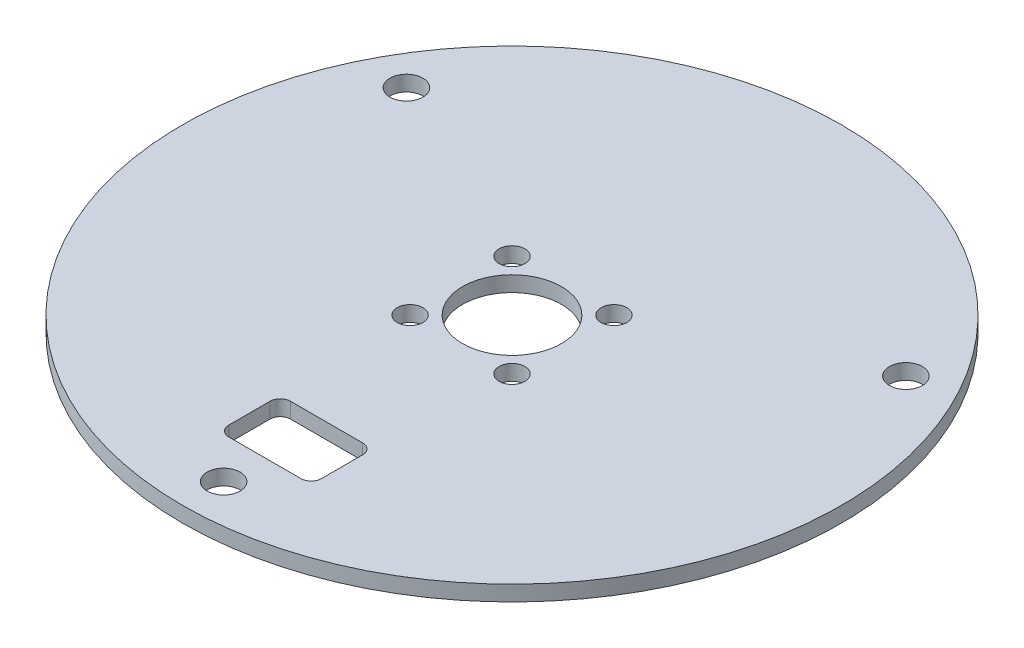
SolidWorks part; units mm, degrees
note: The reader was unsure of these and kept them because the rebuilt part matched: thickness of "Base-Flange1", "Sheet-Metal1", "Sheet-Metal2", "Sheet-Metal3", "Sheet-Metal4".
ref_plane "Front Plane" through (0, 0, 0) normal (0, 0, 1) x (1, 0, 0)
ref_plane "Top Plane" through (0, 0, 0) normal (0, 1, 0) x (1, 0, 0)
ref_plane "Right Plane" through (0, 0, 0) normal (1, 0, 0) x (0, 0, -1)
sketch "Sketch1" plane through (0, 0, 0) normal (0, 1, 0) x (1, 0, 0)
  circle A1 centre (0, 0) radius 32
  dimension "D2" = 64
base flange "Base-Flange1" sketch "Sketch1" thickness 1.5 reverse thickness direction no parameters "D1"=1.5
sketch "Sketch6" plane through (0, 0, 0) normal (0, 1, 0) x (1, 0, 0)
  line L0 (0, 0) -> (0, -28) construction
  line L5 (0, 0) -> (-24.2487, 14) construction
  line L7 (0, 0) -> (24.2487, 14) construction
  circle A10 centre (0, -28) radius 1.6
  circle A11 centre (-24.2487, 14) radius 1.6
  circle A12 centre (24.2487, 14) radius 1.6
  point P9 (0, 0)
  dimension "D1" = 28
  dimension "D2" = 3
  dimension "D3" = 3.2
extrude "Cut-Extrude1" cut sketch "Sketch6" against normal through all normal cut yes
sketch "Sketch7" plane through (0, 0, 0) normal (0, 1, 0) x (1, 0, 0)
  line L1 (4.9497, -4.9497) -> (-4.9497, -4.9497) construction
  line L2 (4.9497, -4.9497) -> (4.9497, 4.9497) construction
  line L3 (4.9497, 4.9497) -> (-4.9497, 4.9497) construction
  line L4 (-4.9497, -4.9497) -> (-4.9497, 4.9497) construction
  line L5 (4.9497, -4.9497) -> (-4.9497, 4.9497) construction
  line L6 (4.9497, 4.9497) -> (-4.9497, -4.9497) construction
  circle A0 centre (0, 0) radius 4.8
  circle A1 centre (-4.9497, 4.9497) radius 1.25
  circle A2 centre (4.9497, 4.9497) radius 1.25
  circle A3 centre (4.9497, -4.9497) radius 1.25
  circle A4 centre (-4.9497, -4.9497) radius 1.25
  dimension "D1" = 9.6
  dimension "D2" = 2.5
  dimension "D3" = 14
extrude "Cut-Extrude2" cut sketch "Sketch7" against normal through all normal cut yes
sketch "Sketch9" plane through (0, 0, 0) normal (0, 1, 0) x (1, 0, 0)
  line L0 (-4.5, -21) -> (4.5, -21) construction
  line L1 (-4.5, -18) -> (4.5, -18)
  line L2 (-4.5, -18) -> (-4.5, -24)
  line L3 (-4.5, -24) -> (4.5, -24)
  line L4 (4.5, -18) -> (4.5, -24)
  point P4 (0, -18)
  dimension "D1" = 6
  dimension "D2" = 9
  dimension "D3" = 21
extrude "Cut-Extrude3" cut sketch "Sketch9" against normal through all normal cut yes
fillet "Fillet1" radius 1 4 edges at (-4.5, -0.75, 24) (4.5, -0.75, 24) (-4.5, -0.75, 18) (4.5, -0.75, 18)
sketch "Bend-Lines1" [suppressed] plane through (0, 0, 0) normal (0, 1, 0) x (1, 0, 0)
sketch "Bounding-Box1" [suppressed] plane through (0, 0, 0) normal (0, 1, 0) x (1, 0, 0)
sheet metal parameters "Sheet-Metal1" thickness 1.5 parameters "D1"=2, "D7"=2
flat pattern "Flat-Pattern1" [suppressed]
sketch "Bend-Lines2" plane through (0, 0, 0) normal (0, 1, 0) x (1, 0, 0)
sketch3d "Bounding-Box2" [suppressed]
  line L0 (32.05, -31.9499, 0) -> (-31.9499, -32.0499, 0) construction
  line L1 (31.95, 32.05, 0) -> (-32.0499, 31.95, 0) construction
  line L2 (32.05, -31.9499, 0) -> (31.95, 32.05, 0) construction
  line L3 (-31.9499, -32.0499, 0) -> (-32.0499, 31.95, 0) construction
sheet metal parameters "Sheet-Metal2" thickness 1.5 parameters "D1"=2, "D7"=2
flat pattern "Flat-Pattern1"
sketch "Bend-Lines2" plane through (0, 0, 0) normal (0, 1, 0) x (1, 0, 0)
sketch3d "Bounding-Box2" [suppressed]
  line L0 (32.05, -31.9499, 0) -> (-31.9499, -32.0499, 0) construction
  line L1 (31.95, 32.05, 0) -> (-32.0499, 31.95, 0) construction
  line L2 (32.05, -31.9499, 0) -> (31.95, 32.05, 0) construction
  line L3 (-31.9499, -32.0499, 0) -> (-32.0499, 31.95, 0) construction
sheet metal parameters "Sheet-Metal3" thickness 1.5 parameters "D1"=2, "D7"=2
flat pattern "Flat-Pattern1"
sketch "Bend-Lines2" plane through (0, 0, 0) normal (0, 1, 0) x (1, 0, 0)
sketch3d "Bounding-Box2" [suppressed]
  line L0 (32.05, -31.9499, 0) -> (-31.9499, -32.0499, 0) construction
  line L1 (31.95, 32.05, 0) -> (-32.0499, 31.95, 0) construction
  line L2 (32.05, -31.9499, 0) -> (31.95, 32.05, 0) construction
  line L3 (-31.9499, -32.0499, 0) -> (-32.0499, 31.95, 0) construction
sheet metal parameters "Sheet-Metal4" thickness 1.5 parameters "D1"=2, "D7"=2
flat pattern "Flat-Pattern1"
sketch "Bend-Lines2" plane through (0, 0, 0) normal (0, 1, 0) x (1, 0, 0)
sketch3d "Bounding-Box2" [suppressed]
  line L0 (32.05, -31.9499, 0) -> (-31.9499, -32.0499, 0) construction
  line L1 (31.95, 32.05, 0) -> (-32.0499, 31.95, 0) construction
  line L2 (32.05, -31.9499, 0) -> (31.95, 32.05, 0) construction
  line L3 (-31.9499, -32.0499, 0) -> (-32.0499, 31.95, 0) construction
